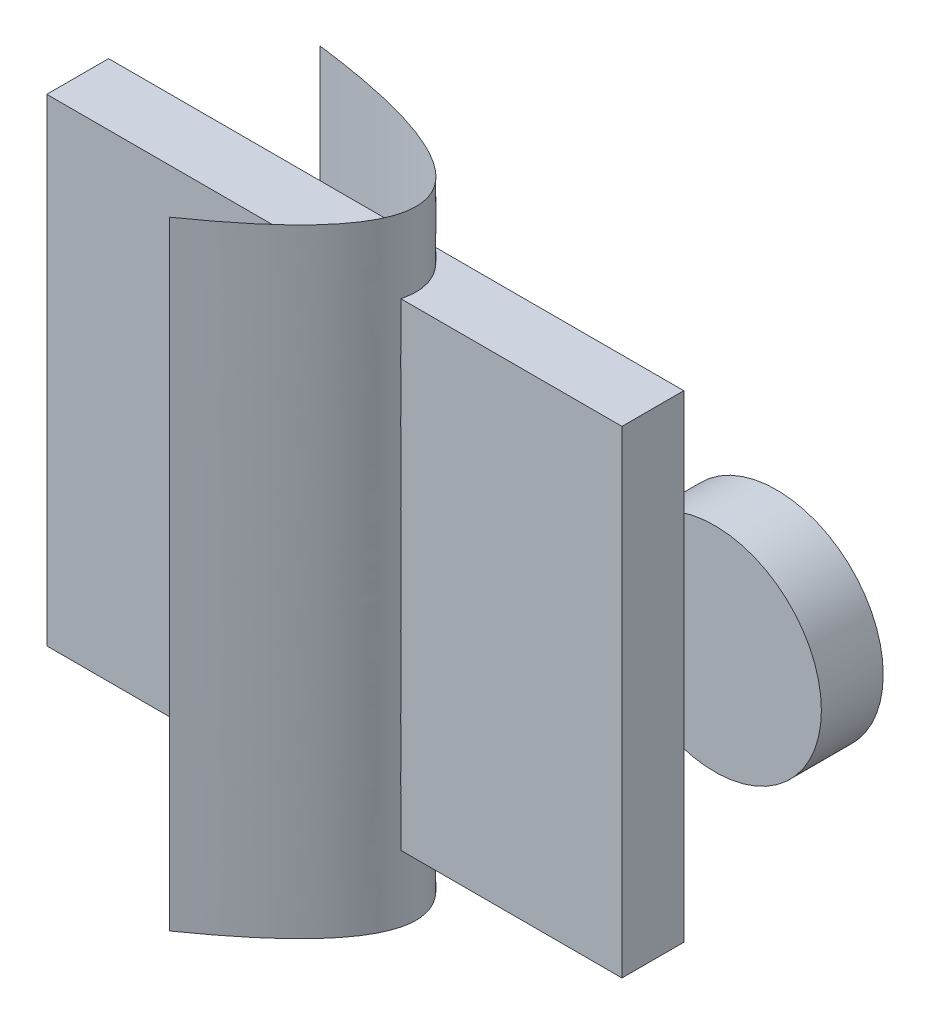
SolidWorks part; units mm, degrees
ref_plane "Спереди" through (0, 0, 0) normal (0, 0, 1) x (1, 0, 0)
ref_plane "Сверху" through (0, 0, 0) normal (0, 1, 0) x (1, 0, 0)
ref_plane "Справа" through (0, 0, 0) normal (1, 0, 0) x (0, 0, -1)
sketch "Эскиз1_fr" plane through (0, 0, 0) normal (0, 0, 1) x (1, 0, 0)
  line L1 (-48.994, 38.0205) -> (44.0482, 38.0205)
  line L2 (-48.994, 38.0205) -> (-48.994, -39.257)
  line L3 (-48.994, -39.257) -> (44.0482, -39.257)
  line L4 (44.0482, 38.0205) -> (44.0482, -39.257)
extrude "Бобышка-Вытянуть1" add sketch "Эскиз1_fr" along normal blind 10
ref_plane "Плоскость4" through (0, 0, -5) normal (0, 0, 1) x (1, 0, 0)
sketch "Эскиз5" plane through (0, 0, -5) normal (0, 0, 1) x (1, 0, 0)
  line L0 (44.0482, -39.257) -> (44.0482, 38.0205) construction
  circle A0 centre (44.0482, -0.6182) radius 17.2618
extrude "Бобышка-Вытянуть2" add sketch "Эскиз5" against normal blind 10 separate body
ref_plane "Плоскость5" through (0, 0, 20) normal (0, 0, 1) x (1, 0, 0)
sketch "Эскиз6" plane through (0, 0, 20) normal (0, 0, 1) x (1, 0, 0)
  line L0 (44.0482, -39.257) -> (44.0482, 38.0205) construction
  line L1 (50.2984, -11.4439) -> (56.5486, -0.6182)
  line L2 (56.5486, -0.6182) -> (50.2984, 10.2074)
  line L3 (50.2984, 10.2074) -> (37.798, 10.2074)
  line L4 (37.798, 10.2074) -> (31.5478, -0.6182)
  line L5 (31.5478, -0.6182) -> (37.798, -11.4439)
  line L6 (37.798, -11.4439) -> (50.2984, -11.4439)
  circle A0 centre (44.0482, -0.6182) radius 10.8257 construction
sketch "Эскиз7" plane through (0, 0, 0) normal (0, 1, 0) x (1, 0, 0)
  spline S0 degree 2 poles (-9.8895, -29.2716) (32.2081, 0.1563) (-21.677, 6.8901) knots 0 0 0 1 1 1
surface "Поверхность-Вытянуть1" sketch "Эскиз7" parameters "D1"=50, "D2"=50
split "Разделить1" trimming surface bodies 106 bodies to split 103 resulting bodies 107 108
